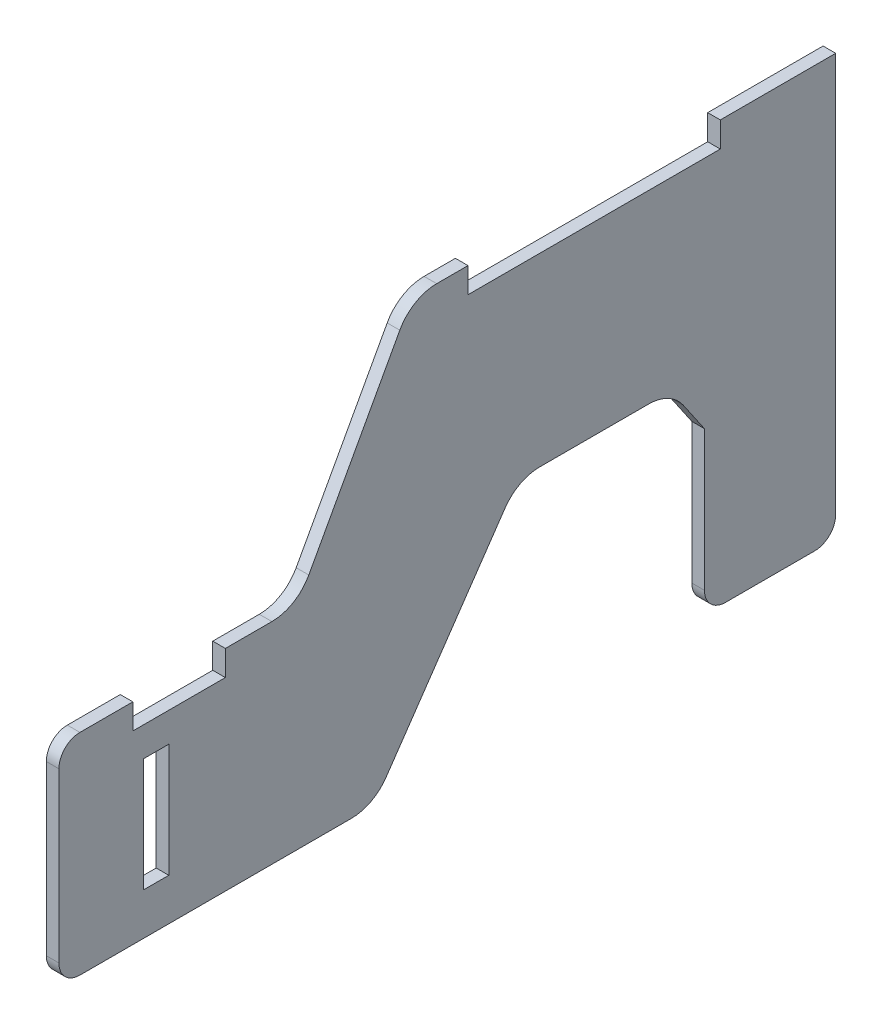
SolidWorks part; units mm, degrees
ref_plane "Front Plane" through (0, 0, 0) normal (0, 0, 1) x (1, 0, 0)
ref_plane "Top Plane" through (0, 0, 0) normal (0, 1, 0) x (1, 0, 0)
ref_plane "Right Plane" through (0, 0, 0) normal (1, 0, 0) x (0, 0, -1)
sketch "Sketch2" plane through (0, 0, 0) normal (1, 0, 0) x (0, 0, -1)
  line L10 (54.4314, -85.4988) -> (76.074, -45.9059)
  line L20 (84.8486, -40.7023) -> (92.2965, -40.7023)
  line L21 (122.2965, -65.5687) -> (122.2965, -90.7023) construction
  line L22 (135.2324, -90.7023) -> (109.3606, -90.7023)
  line L23 (72.8068, -136.355) -> (101.1115, -95.0496)
  line L24 (190.1616, -85.4988) -> (168.519, -45.9059)
  line L25 (171.7862, -136.355) -> (143.4815, -95.0496)
  line L29 (92.2965, -40.7023) -> (92.2965, -46.7023)
  line L30 (92.2965, -46.7023) -> (152.2965, -46.7023)
  line L31 (152.2965, -40.7023) -> (152.2965, -46.7023)
  line L32 (152.2965, -40.7023) -> (159.7444, -40.7023)
  line L33 (39.6219, -90.7023) -> (45.6568, -90.7023)
  line L34 (12.587, -90.7023) -> (12.587, -96.7023)
  line L35 (12.587, -96.7023) -> (34.587, -96.7023)
  line L38 (232.006, -96.7023) -> (210.006, -96.7023)
  line L39 (232.006, -90.7023) -> (232.006, -96.7023)
  line L40 (204.9711, -90.7023) -> (198.9363, -90.7023)
  line L41 (23.587, -103.0419) -> (23.587, -139.1323) construction
  line L45 (18.3738, -140.7023) -> (18.3738, -117.2023) construction
  line L55 (34.587, -96.7023) -> (34.587, -90.7023)
  line L56 (34.587, -90.7023) -> (39.6219, -90.7023)
  line L57 (210.006, -96.7023) -> (210.006, -90.7023)
  line L58 (210.006, -90.7023) -> (204.9711, -90.7023)
  line L60 (-5, -95.7023) -> (-5, -135.7023)
  line L62 (251.0185, -95.9566) -> (248.9813, -135.9566)
  line L65 (232.006, -90.7023) -> (246.025, -90.7023)
  line L66 (180.0352, -140.7023) -> (243.9878, -140.7023)
  line L67 (0, -140.7023) -> (64.5578, -140.7023)
  line L68 (0, -90.7023) -> (12.587, -90.7023)
  line L69 (223.463, -130.7023) -> (229.463, -130.7023)
  line L70 (21.13, -103.7023) -> (15.13, -103.7023)
  line L71 (21.13, -103.7023) -> (21.13, -130.7023)
  line L72 (21.13, -130.7023) -> (15.13, -130.7023)
  line L73 (15.13, -103.7023) -> (15.13, -130.7023)
  line L74 (229.463, -103.7023) -> (229.463, -130.7023)
  line L75 (223.463, -103.7023) -> (229.463, -103.7023)
  line L76 (223.463, -103.7023) -> (223.463, -130.7023)
  arc A0 (76.074, -45.9059) -> (84.8486, -40.7023) centre (84.8486, -50.7023) cw
  arc A2 (72.8068, -136.355) -> (64.5578, -140.7023) centre (64.5578, -130.7023) cw
  arc A3 (101.1115, -95.0496) -> (109.3606, -90.7023) centre (109.3606, -100.7023) cw
  arc A4 (45.6568, -90.7023) -> (54.4314, -85.4988) centre (45.6568, -80.7023) ccw
  arc A6 (143.4815, -95.0496) -> (135.2324, -90.7023) centre (135.2324, -100.7023) ccw
  arc A7 (168.519, -45.9059) -> (159.7444, -40.7023) centre (159.7444, -50.7023) ccw
  arc A8 (198.9363, -90.7023) -> (190.1616, -85.4988) centre (198.9363, -80.7023) cw
  arc A9 (171.7862, -136.355) -> (180.0352, -140.7023) centre (180.0352, -130.7023) ccw
  arc A11 (251.0185, -95.9566) -> (246.025, -90.7023) centre (246.025, -95.7023) ccw
  arc A12 (248.9813, -135.9566) -> (243.9878, -140.7023) centre (243.9878, -135.7023) cw
  arc A13 (-5, -135.7023) -> (0, -140.7023) centre (0, -135.7023) ccw
  arc A14 (-5, -95.7023) -> (0, -90.7023) centre (0, -95.7023) cw
  point P10 (78.9184, -40.7023)
  point P14 (1.587, -90.7023)
  point P17 (71.587, -140.7023)
  point P22 (51.587, -90.7023)
  point P25 (1.587, -140.7023)
  point P48 (122.2965, -46.7023)
  point P56 (23.587, -96.7023)
  point P67 (23.587, -133.7023)
  point P68 (23.587, -106.7023)
  dimension "D4" = 10
  dimension "D5" = 10
  dimension "D7" = 10
  dimension "D9" = 5
  dimension "D19" = 5
  dimension "D20" = 5
  dimension "D17" = 5
  dimension "D1" = 50
  dimension "D2" = 50
  dimension "D3" = 50
  dimension "D6" = 70
  dimension "D8" = 100
  dimension "D10" = 56.9825
  dimension "D11" = 6
  dimension "D12" = 30
  dimension "D13" = 11
  dimension "D14" = 6
  dimension "D15" = 100
  dimension "D16" = 23.5
  dimension "D21" = 6
  dimension "D22" = 20.13
extrude "Boss-Extrude1" add sketch "Sketch2" along normal blind 3
sketch "Sketch3" plane through (0, 0, 0) normal (1, 0, 0) x (0, 0, -1)
  line L0 (159.7444, -40.7023) -> (159.7444, -144.4609)
  line L1 (159.7444, -144.4609) -> (257.8753, -144.4609)
  line L2 (257.8753, -144.4609) -> (257.8753, -25.5441)
  line L3 (257.8753, -25.5441) -> (159.7444, -34.9038)
  line L4 (159.7444, -34.9038) -> (159.7444, -40.7023)
extrude "Cut-Extrude1" cut sketch "Sketch3" along normal blind 10
sketch "Sketch4" plane through (0, 0, 0) normal (1, 0, 0) x (0, 0, -1)
  line L0 (159.7444, -40.7023) -> (179.7444, -40.7023)
  line L1 (179.7444, -40.7023) -> (179.7444, -135.7023)
  line L2 (153.525, -140.7023) -> (174.7444, -140.7023)
  line L3 (148.525, -102.4097) -> (148.525, -135.7023)
  line L4 (143.4815, -95.0496) -> (159.7444, -118.7823) construction
  line L5 (159.7444, -40.7023) -> (148.525, -102.4097)
  arc A0 (174.7444, -140.7023) -> (179.7444, -135.7023) centre (174.7444, -135.7023) ccw
  arc A1 (148.525, -135.7023) -> (153.525, -140.7023) centre (153.525, -135.7023) ccw
  dimension "D2" = 5
  dimension "D1" = 20
extrude "Boss-Extrude2" add sketch "Sketch4" along normal blind 3
